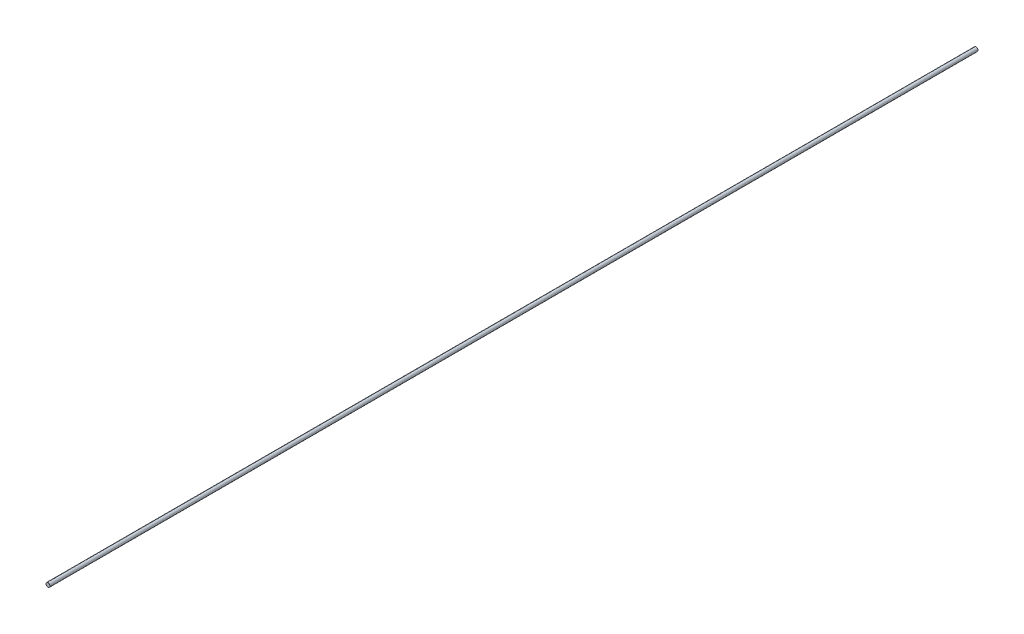
SolidWorks part; units mm, degrees
ref_plane "Plan de face" through (0, 0, 0) normal (0, 0, 1) x (1, 0, 0)
ref_plane "Plan de dessus" through (0, 0, 0) normal (0, 1, 0) x (1, 0, 0)
ref_plane "Plan de droite" through (0, 0, 0) normal (1, 0, 0) x (0, 0, -1)
sketch "Esquisse1" plane through (0, 0, 0) normal (0, 0, 1) x (1, 0, 0)
  circle A0 centre (0, 0) radius 1.5
  dimension "D1" = 3
extrude "Boss.-Extru.1" add sketch "Esquisse1" along normal blind 700
